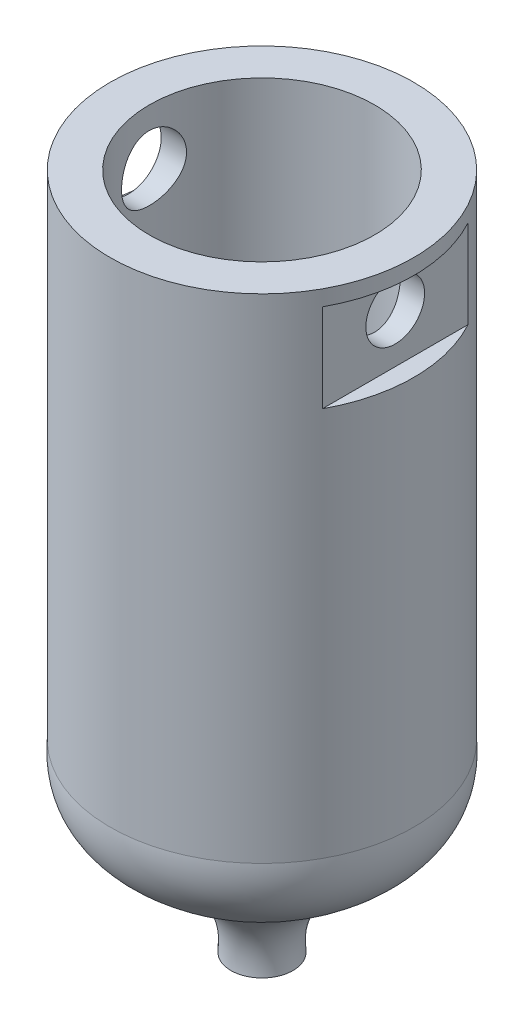
SolidWorks part; units mm, degrees
ref_plane "Front Plane" through (0, 0, 0) normal (0, 0, 1) x (1, 0, 0)
ref_plane "Top Plane" through (0, 0, 0) normal (0, 1, 0) x (1, 0, 0)
ref_plane "Right Plane" through (0, 0, 0) normal (1, 0, 0) x (0, 0, -1)
sketch "Sketch1" plane through (0, 0, 0) normal (0, 0, 1) x (1, 0, 0)
  line L0 (0, 0) -> (1, 0)
  line L1 (0, 0) -> (0, -12)
  line L3 (1, 0) -> (1, -12)
  line L4 (1, -12) -> (1, -12.6028)
  line L5 (3.8791, 0) -> (3.8791, -20.2273) construction
  line L6 (3.084, -17.3166) -> (3.4563, -17.3166)
  spline S0 degree 1 poles (0, -12) (0, -12.6028) knots 0 0 1 1
  spline S1 degree 3 poles (0, -12.6028) (-0.2171, -15.2492) (3.3418, -14.7278) (3.084, -17.3166) knots 0 0 0 0 1 1 1 1
  spline S2 degree 3 poles (1, -12.6028) (0.7984, -14.1895) (4.0525, -14.1586) (3.3564, -16.6777) (3.4563, -17.3166) knots 0 0 0 0 0.610594 1 1 1 1
  dimension "D1" = 1
  dimension "D2" = 12
  dimension "D3" = 3.8791
revolve "Revolve1" add sketch "Sketch1" angle 360 about L5
sketch "Sketch2" plane through (0, 0, 0) normal (0, 1, 0) x (1, 0, 0)
  circle A0 centre (3.8791, 0) radius 3.8791
ref_plane "Plane1" through (3.8791, 0, 0) normal (1, 0, 0) x (0, 0, -1)
ref_plane "Plane2" through (7.7582, 0, 0) normal (1, 0, 0) x (0, 0, -1)
sketch "Sketch3" plane through (7.7582, 0, 0) normal (1, 0, 0) x (0, 0, -1)
  circle A0 centre (0, -1.4) radius 0.75
  dimension "D1" = 1.5
  dimension "D2" = 1.4
extrude "Cut-Extrude1" cut sketch "Sketch3" against normal blind 5 and the other way through all
sketch "Sketch4" plane through (0, 0, 0) normal (0, 1, 0) x (1, 0, 0)
  circle A0 centre (3.8791, 0) radius 3.8652
ref_plane "Plane3" through (-0.0209, 0, 0) normal (1, 0, 0) x (0, 0, -1)
sketch "Sketch5" plane through (-0.0209, 0, 0) normal (1, 0, 0) x (0, 0, -1)
  circle A0 centre (0, -1.4) radius 0.83
  dimension "D1" = 1.4
extrude "Cut-Extrude3" cut sketch "Sketch5" along normal blind 5
sketch "Sketch6" plane through (0, 0, 0) normal (0, 0, 1) x (1, 0, 0)
  line L0 (0, 0) -> (0, -0.57) construction
  line L1 (0, -0.3983) -> (0.4752, -0.3983)
  line L2 (0, -0.3983) -> (0, -2.6522)
  line L3 (0, -2.6522) -> (0.4752, -2.6522)
  line L4 (0.4752, -0.3983) -> (0.4752, -2.6522)
  line L5 (0, -0.3983) -> (0.4752, -2.6522) construction
  line L6 (0, -2.6522) -> (0.4752, -0.3983) construction
  line L7 (7.7582, 0) -> (0, 0) construction
  line L8 (7.7582, 0) -> (0, 0)
  line L9 (3.8791, 3.4441) -> (3.8791, -5.3589) construction
  line L10 (7.7582, -2.6522) -> (7.2831, -0.3983) construction
  line L11 (7.7582, -0.3983) -> (7.2831, -2.6522) construction
  line L12 (7.2831, -0.3983) -> (7.2831, -2.6522)
  line L13 (7.7582, -2.6522) -> (7.2831, -2.6522)
  line L14 (7.7582, -0.3983) -> (7.7582, -2.6522)
  line L15 (7.7582, -0.3983) -> (7.2831, -0.3983)
  point P4 (0.2376, -1.5253)
  point P9 (3.8791, 0)
  point P16 (7.5206, -1.5253)
extrude "Cut-Extrude4" cut sketch "Sketch6" against normal blind 10 and the other way blind 10 contours L4 L1 L2 L3 | L14 L15 L12 L13 region at (0.2376, -1.5253, 0) region at (7.5206, -1.5253, 0)
